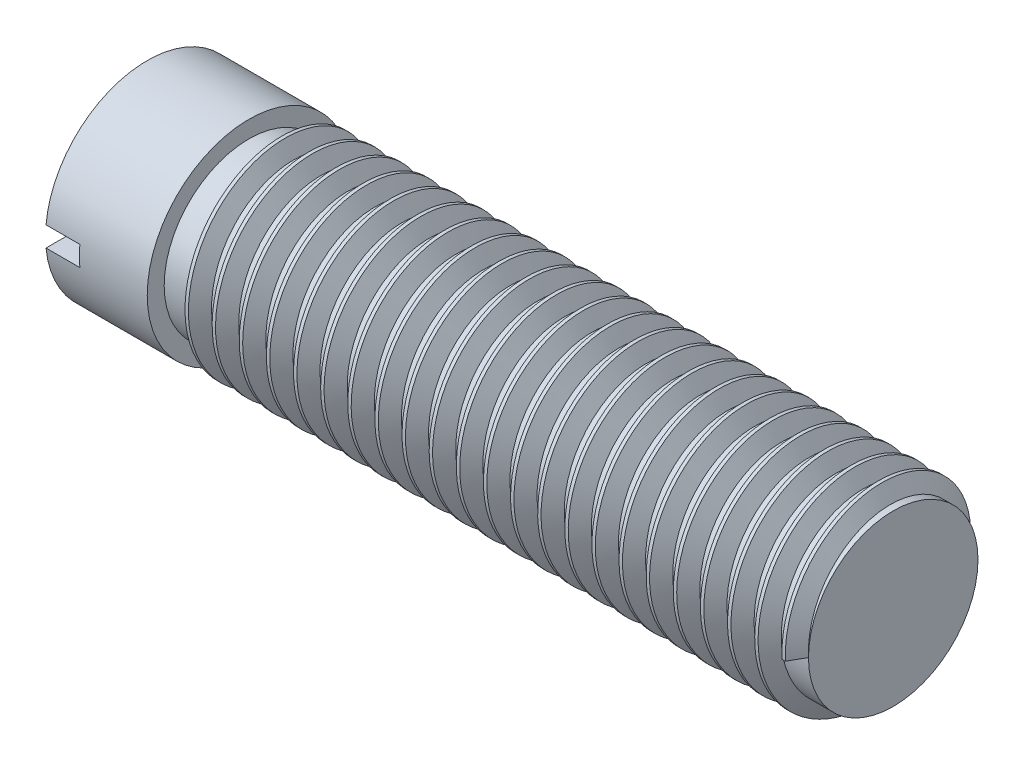
SolidWorks part; units mm, degrees
ref_plane "Front Plane" through (0, 0, 0) normal (0, 0, 1) x (1, 0, 0)
ref_plane "Top Plane" through (0, 0, 0) normal (0, 1, 0) x (1, 0, 0)
ref_plane "Right Plane" through (0, 0, 0) normal (1, 0, 0) x (0, 0, -1)
sketch "Sketch1" plane through (0, 0, 0) normal (0, 0, 1) x (1, 0, 0)
  line L0 (-11, 0) -> (11, 0)
  line L1 (-11, 0) -> (-11, 3)
  line L2 (-11, 3) -> (-8, 3)
  line L3 (-8, 3) -> (-8, 2.5)
  line L4 (-8, 2.5) -> (11, 2.5)
  line L5 (11, 2.5) -> (11, 0)
  point P3 (0, 0)
  dimension "D1" = 22
  dimension "D2" = 3
  dimension "D3" = 2.5
revolve "Revolve1" add sketch "Sketch1" angle 360 about L0
sketch "Sketch2" plane through (0, 0, 0) normal (0, 0, 1) x (1, 0, 0)
  line L0 (-11, 3) -> (-11, -3) construction
  line L2 (-12, 0.2959) -> (-10, 0.2959)
  line L3 (-12, 0.2959) -> (-12, -0.2959)
  line L4 (-12, -0.2959) -> (-10, -0.2959)
  line L5 (-10, 0.2959) -> (-10, -0.2959)
  line L6 (-12, 0.2959) -> (-10, -0.2959) construction
  line L7 (-12, -0.2959) -> (-10, 0.2959) construction
  point P1 (-11, 0)
  point P7 (0, 0)
  dimension "D1" = 2
  dimension "D2" = 0.2959
extrude "Cut-Extrude1" cut sketch "Sketch2" against normal through all both and the other way through all
thread "Thread2" pitch 0.8 method extrude profile "Thread Profile2" start angle 0, offset 0, length 18, pitch 0.8, diameter 5
ref_plane "Plane2" through (11, 0, 2.5) normal (0, -1, 0) x (0, 0, 1)
sketch "Thread Profile2" plane through (11, 0, 2.5) normal (0, -1, 0) x (0, 0, 1)
  line L0 (0, 0) -> (0, 0.8) construction
  line L1 (0, 0) -> (0.433, 0.25)
  line L2 (0.433, 0.25) -> (0.433, 0.35)
  line L3 (0.433, 0.35) -> (0, 0.6)
  line L4 (0.433, 0.3) -> (0, 0.3) construction
  line L11 (0, 0) -> (0, 0.6)
  point P2 (0, 0)
  dimension "Pitch" = 0.8
  dimension "Profile_Angle" = 60
  dimension "Profile_Land" = 0.1
  dimension "Profile_Height" = 0.433
